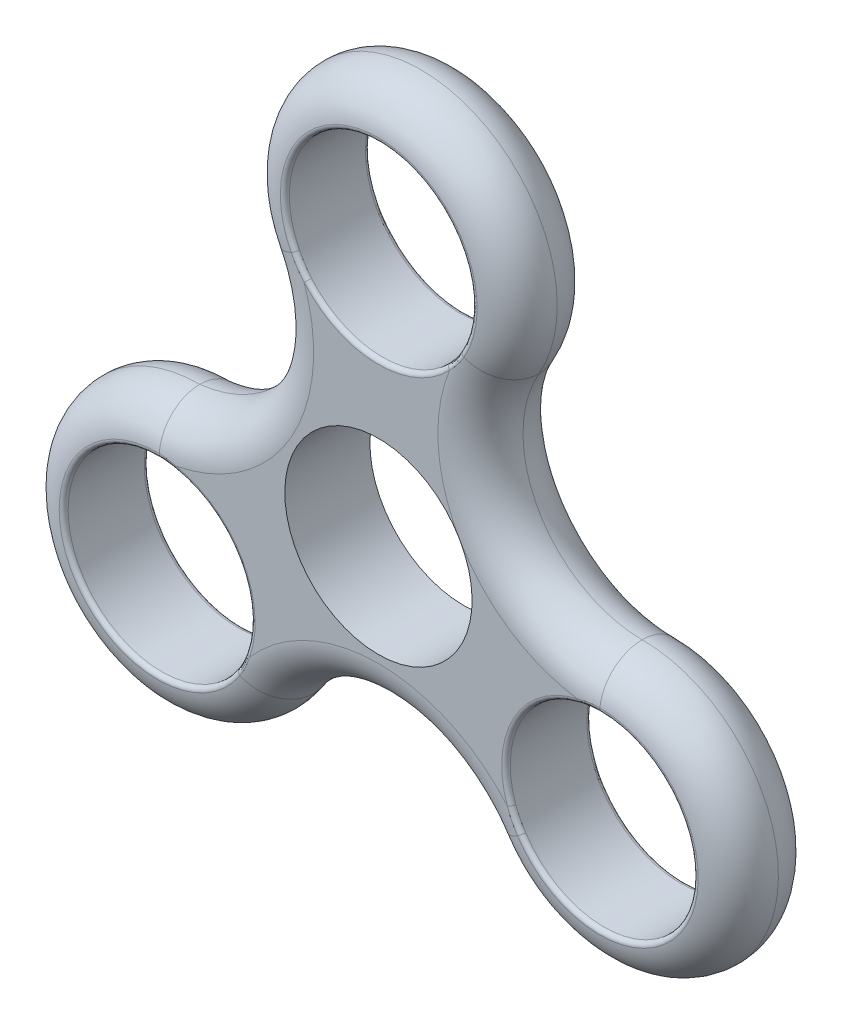
SolidWorks part; units mm, degrees
ref_plane "Front Plane" through (0, 0, 0) normal (0, 0, 1) x (1, 0, 0)
ref_plane "Top Plane" through (0, 0, 0) normal (0, 1, 0) x (1, 0, 0)
ref_plane "Right Plane" through (0, 0, 0) normal (1, 0, 0) x (0, 0, -1)
sketch "Sketch1" plane through (0, 0, 0) normal (0, 0, 1) x (1, 0, 0)
  line L0 (0, 30) -> (0, -23.9622) construction
  circle A0 centre (0, 0) radius 11
  circle A1 centre (0, 30) radius 11
  circle A2 centre (25.9808, -15) radius 11
  circle A3 centre (-25.9808, -15) radius 11
  circle A4 centre (0, 30) radius 16
  circle A5 centre (-25.9808, -15) radius 16
  circle A6 centre (25.9808, -15) radius 16
  arc A7 (-12.5713, -23.7285) -> (12.5713, -23.7285) centre (0, -31.9115) cw
  arc A8 (-25.9808, 1) -> (-14.2521, 22.7282) centre (-27.6133, 15.9109) ccw
  arc A9 (13.8564, 22) -> (25.9808, 1) centre (25.9808, 15) ccw
  point P13 (0, 0)
  dimension "D1" = 22
  dimension "D2" = 30
  dimension "D5" = 15
  dimension "D6" = 15
  dimension "D7" = 14
  dimension "D4" = 5
  dimension "D3" = 3
extrude "Boss-Extrude1" add sketch "Sketch1" along normal blind 10 contours A1 A4 | A5 A3 | A6 A2 | A4 L0 A0 A7 A6 A9 | L0 A4 A8 A5 A7 A0 region at (-8.1198, 16.7414, 0) region at (8.263, 15.6881, 0) region at (-0.5323, 12.5, 0) region at (-14.9871, -4.0063, 0) region at (36.9745, -4.0063, 0)
fillet "Fillet10" radius 5 6 edges at (-14.4136, 8.7858, 0) (0.4144, 45.9946, 0) (-40.0459, -22.627, 0) (0, -16.9115, 0) (40.0459, -22.627, 0) (13.8564, 8, 0)
fillet "Fillet11" radius 5 6 edges at (-40.0459, -22.627, 10) (-14.4136, 8.7858, 10) (0.4144, 45.9946, 10) (13.8564, 8, 10) (40.0459, -22.627, 10) (0, -16.9115, 10)
fillet "Fillet16" radius 0.5 12 edges at (-16.2571, -9.857, 0) (-35.7044, -20.143, 0) (-16.2571, -9.857, 10) (-35.7044, -20.143, 10) (0.2849, 40.9963, 0) (-0.2849, 19.0037, 0) (0.2849, 40.9963, 10) (-0.2849, 19.0037, 10) (35.6505, -20.2436, 0) (16.311, -9.7564, 0) (35.6505, -20.2436, 10) (16.311, -9.7564, 10)
